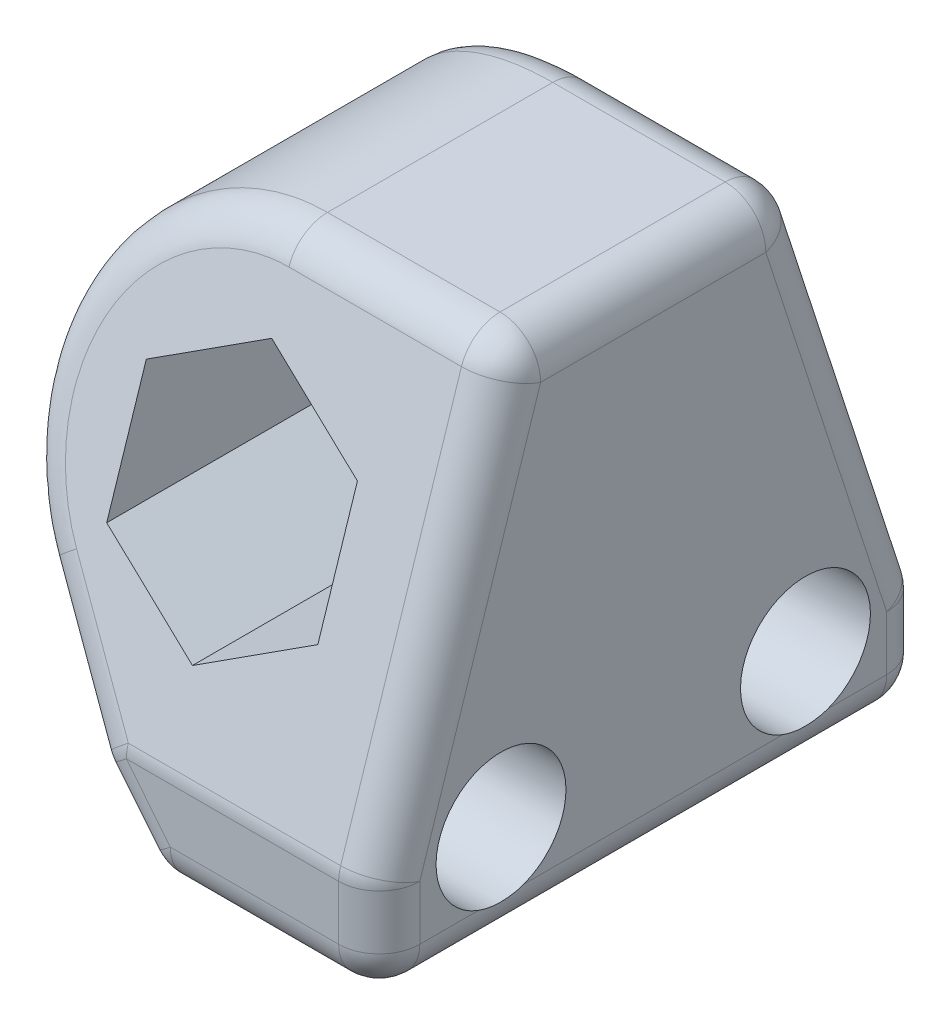
SolidWorks part; units mm, degrees
ref_plane "Front Plane" through (0, 0, 0) normal (0, 0, 1) x (1, 0, 0)
ref_plane "Top Plane" through (0, 0, 0) normal (0, 1, 0) x (1, 0, 0)
ref_plane "Right Plane" through (0, 0, 0) normal (1, 0, 0) x (0, 0, -1)
sketch "Sketch1" plane through (0, 0, 0) normal (0, 0, 1) x (1, 0, 0)
  line L0 (0, 0) -> (0, 15.875)
  line L2 (-3.3655, 11.4314) -> (-6.6675, 13.3378)
  line L3 (-6.6675, 13.3378) -> (-9.9695, 11.4314)
  line L4 (-9.9695, 11.4314) -> (-9.9695, 7.6186)
  line L5 (-9.9695, 7.6186) -> (-6.6675, 5.7122)
  line L6 (-6.6675, 5.7122) -> (-3.3655, 7.6186)
  line L7 (-3.3655, 7.6186) -> (-3.3655, 11.4314)
  line L8 (-6.6675, 15.875) -> (0, 15.875)
  line L9 (0, 0) -> (-7.1437, 0)
  line L11 (-11.6105, 5.5388) -> (-7.1437, 0)
  circle A0 centre (-6.6675, 9.525) radius 3.302 construction
  arc A1 (-6.6675, 15.875) -> (-11.6105, 5.5388) centre (-6.6675, 9.525) ccw
  point P14 (-11.4867, 5.3854)
  dimension "D5" = 6.35
  dimension "D1" = 6.604
  dimension "D3" = 9.525
  dimension "D4" = 6.6675
  dimension "D6" = 7.1437
extrude "Boss-Extrude1" add sketch "Sketch1" along normal mid plane 17.145
sketch "Sketch2" plane through (0, 0, 0) normal (1, 0, 0) x (0, 0, -1)
  line L0 (-4.7625, 3.175) -> (4.7625, 3.175)
  circle A0 centre (-4.7625, 3.175) radius 2.032
  circle A1 centre (4.7625, 3.175) radius 2.032
  point P4 (0, 3.175)
  point P5 (4.7625, 3.1851)
  dimension "D1" = 4.064
  dimension "D2" = 9.525
  dimension "D3" = 3.175
extrude "Cut-Extrude1" cut sketch "Sketch2" against normal through all contours A0 | A1
sketch "Sketch3" plane through (0, 0, 0) normal (1, 0, 0) x (0, 0, -1)
  line L0 (-4.445, 15.875) -> (-8.5725, 15.875)
  line L1 (-8.5725, 15.875) -> (8.5725, 15.875) construction
  line L2 (-8.5725, 15.875) -> (-8.5725, 3.175)
  line L3 (-8.5725, 0) -> (-8.5725, 15.875) construction
  line L4 (-8.5725, 3.175) -> (-4.445, 15.875)
  line L5 (0, 15.875) -> (0, 14.2537) construction
  line L6 (8.5725, 15.875) -> (8.5725, 3.175)
  line L7 (4.445, 15.875) -> (8.5725, 15.875)
  line L8 (8.5725, 3.175) -> (4.445, 15.875)
  dimension "D1" = 12.7
  dimension "D2" = 4.1275
extrude "Cut-Extrude2" cut sketch "Sketch3" against normal through all
fillet "Fillet1" radius 1.27 18 edges at (-10.6573, 4.3569, -8.1884) (-12.3961, 12.2645, -5.6184) (-10.6573, 4.3569, 8.1884) (-3.3337, 15.875, -4.445) (0, 15.875, 0) (-3.3337, 15.875, 4.445) (0, 1.5875, 8.5725) (-3.5719, 0, 8.5725) (-8.424, 1.5875, 8.5725) (-4.8521, 3.175, 8.5725) (-3.5719, 0, -8.5725) (-4.8521, 3.175, -8.5725) (0, 9.525, -6.5088) (-12.3961, 12.2645, 5.6184) (-7.1437, 0, 0) (0, 1.5875, -8.5725) (0, 0, 0) (0, 9.525, 6.5087)
